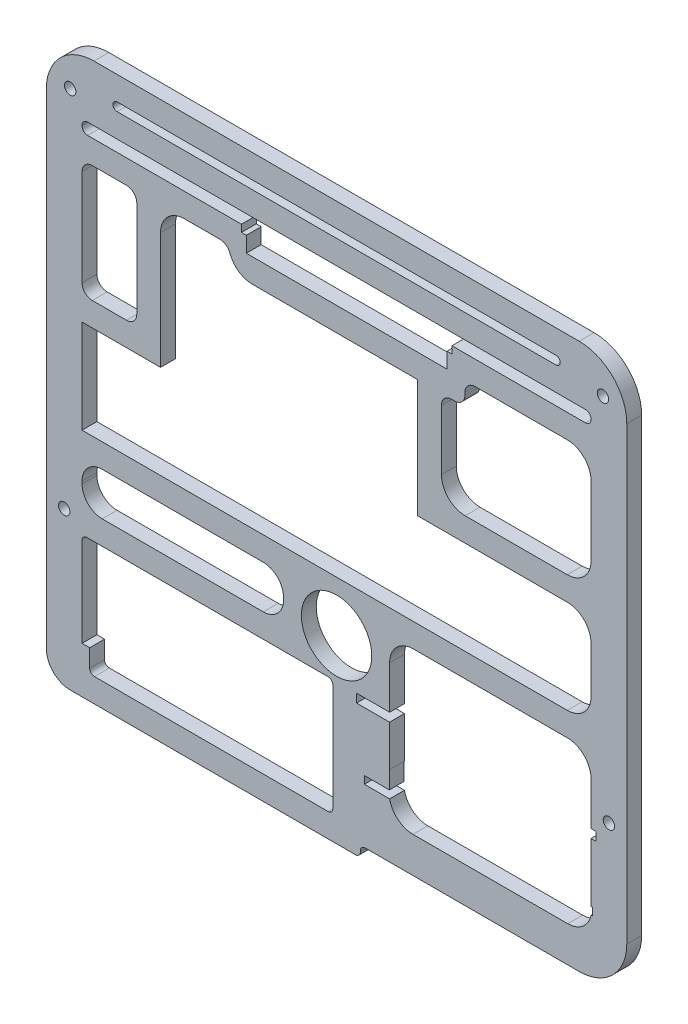
SolidWorks part; units mm, degrees
ref_plane "Front Plane" through (0, 0, 0) normal (0, 0, 1) x (1, 0, 0)
ref_plane "Top Plane" through (0, 0, 0) normal (0, 1, 0) x (1, 0, 0)
ref_plane "Right Plane" through (0, 0, 0) normal (1, 0, 0) x (0, 0, -1)
sketch "Sketch1" plane through (0, 0, 0) normal (0, 0, 1) x (1, 0, 0)
  line L0 (63.9883, 61.406) -> (63.9883, 57.596) construction
  line L1 (11.1776, 3.1158) -> (73.1542, 3.1158)
  line L2 (11.1776, 3.1158) -> (11.1776, 61.406)
  line L3 (11.1776, 61.406) -> (73.1542, 61.406)
  line L4 (73.1542, 3.1158) -> (73.1542, 61.406)
  line L5 (69.3442, 57.596) -> (14.9876, 57.596)
  line L6 (69.3442, 57.596) -> (69.3442, 6.9258)
  line L7 (69.3442, 6.9258) -> (14.9876, 6.9258)
  line L8 (14.9876, 57.596) -> (14.9876, 6.9258)
  line L9 (63.9883, 59.501) -> (18.0707, 59.501) construction
  line L10 (14.9876, 39.3805) -> (11.1776, 39.3805) construction
  line L11 (13.0826, 39.3805) -> (13.0826, 23.9527) construction
  line L12 (13.5248, 6.9258) -> (13.5248, 3.1158) construction
  line L13 (13.5248, 5.0208) -> (21.1598, 5.0208) construction
  line L14 (73.1542, 38.1916) -> (69.3442, 38.1916) construction
  line L15 (71.2492, 38.1916) -> (71.2492, 22.3321) construction
  line L16 (55.7422, 59.501) -> (30.5962, 59.501) construction
  line L19 (42.3087, 5.0208) -> (41.7626, 5.0208) construction
  line L21 (69.3442, 16.9588) -> (69.3442, 52.516) construction
  line L22 (14.9876, 47.563) -> (14.9876, 12.0058) construction
  dimension "D1" = 3.81
  dimension "D2" = 3.81
extrude "Boss-Extrude1" add sketch "Sketch1" along normal blind 1.5875
sketch "Sketch2" plane through (0, 0, 0) normal (0, 0, -1) x (-1, 0, 0)
  line L0 (-69.3442, 6.9258) -> (-69.3442, 57.596) construction
  line L1 (-69.3442, 26.6348) -> (-14.9876, 26.6348)
  line L2 (-69.3442, 26.6348) -> (-69.3442, 24.0948)
  line L3 (-69.3442, 24.0948) -> (-14.9876, 24.0948)
  line L4 (-14.9876, 26.6348) -> (-14.9876, 24.0948)
  line L5 (-14.9876, 57.596) -> (-14.9876, 6.9258) construction
  line L6 (-20.1206, 26.6348) -> (-57.8206, 26.6348) construction
  line L7 (-53.9642, 53.4304) -> (-53.9642, 51.7667)
  line L8 (-32.5266, 53.4304) -> (-32.0059, 53.4304)
  line L9 (-32.5266, 51.7667) -> (-53.9642, 51.7667) construction
  line L10 (-32.5266, 51.7667) -> (-32.5266, 53.4304) construction
  line L11 (-69.3442, 54.1924) -> (-54.4849, 54.1924)
  line L12 (-69.3442, 54.1924) -> (-69.3442, 51.6524)
  line L13 (-69.3442, 51.6524) -> (-55.8692, 51.6524)
  line L14 (-14.9876, 54.1924) -> (-14.9876, 51.6524)
  line L15 (-69.3442, 57.596) -> (-14.9876, 57.596)
  line L16 (-69.3442, 57.596) -> (-69.3442, 55.4243)
  line L17 (-69.3442, 55.4243) -> (-14.9876, 55.4243)
  line L18 (-14.9876, 57.596) -> (-14.9876, 55.4243)
  line L19 (-69.3442, 57.596) -> (-14.9876, 57.596) construction
  line L20 (-54.4849, 54.1924) -> (-54.4849, 53.4304)
  line L21 (-62.3462, 55.4243) -> (-23.9922, 55.4243) construction
  line L22 (-54.4849, 53.4304) -> (-53.9642, 53.4304)
  line L23 (-32.5266, 51.7667) -> (-53.9642, 51.7667)
  line L24 (-32.5266, 51.7667) -> (-32.5266, 53.4304)
  line L25 (-55.8692, 51.6524) -> (-55.8692, 49.2267)
  line L26 (-55.8692, 49.2267) -> (-30.6216, 49.2267)
  line L27 (-30.6216, 49.2267) -> (-30.6216, 51.6524)
  line L28 (-30.6216, 51.6524) -> (-14.9876, 51.6524)
  line L29 (-32.0059, 53.4304) -> (-32.0059, 54.1924)
  line L30 (-62.3462, 54.1924) -> (-23.9922, 54.1924) construction
  line L32 (-54.4849, 53.4304) -> (-54.4849, 54.1924) construction
  line L33 (-32.0059, 53.4304) -> (-54.4849, 53.4304) construction
  line L34 (-32.0059, 54.1924) -> (-14.9876, 54.1924)
  line L36 (-32.0059, 53.4304) -> (-32.0059, 54.1924) construction
  line L37 (-32.5266, 51.7667) -> (-32.5266, 53.4304) construction
  dimension "D1" = 2.54
  dimension "D2" = 1.905
  dimension "D3" = 2.54
  dimension "D4" = 1.905
  dimension "D5" = 2.54
extrude "Boss-Extrude2" add sketch "Sketch2" against normal up to surface (1.5875 mm away) up to face at (42.1659, 32.2609, 1.5875)
sketch "Sketch3" plane through (0, 0, 0) normal (0, 0, -1) x (-1, 0, 0)
  line L0 (-57.8206, 36.6348) -> (-50.8206, 36.6348) construction
  line L1 (-57.8206, 36.6348) -> (-50.8206, 36.6348)
  line L2 (-57.8206, 36.6348) -> (-69.3442, 36.6348)
  line L3 (-69.3442, 26.6348) -> (-69.3442, 51.6524) construction
  line L4 (-69.3442, 36.6348) -> (-69.3442, 39.1748)
  line L5 (-69.3442, 39.1748) -> (-53.3606, 39.1748)
  line L6 (-50.8206, 28.408) -> (-50.8206, 36.6348)
  line L7 (-50.8206, 28.408) -> (-50.8206, 49.2267)
  line L8 (-55.8692, 49.2267) -> (-30.6216, 49.2267) construction
  line L9 (-50.8206, 49.2267) -> (-53.3606, 49.2267)
  line L10 (-53.3606, 49.2267) -> (-53.3606, 39.1748)
  line L11 (-23.3706, 36.6348) -> (-20.1206, 36.6348) construction
  line L12 (-23.3706, 36.6348) -> (-20.1206, 36.6348)
  line L13 (-20.1206, 36.6348) -> (-14.9876, 36.6348)
  line L14 (-14.9876, 51.6524) -> (-14.9876, 26.6348) construction
  line L15 (-14.9876, 36.6348) -> (-14.9876, 39.1748)
  line L16 (-14.9876, 39.1748) -> (-20.8306, 39.1748)
  line L17 (-20.8306, 39.1748) -> (-20.8306, 51.6524)
  line L18 (-30.6216, 51.6524) -> (-14.9876, 51.6524) construction
  line L19 (-20.8306, 51.6524) -> (-23.3706, 51.6524)
  line L20 (-23.3706, 51.6524) -> (-23.3706, 36.6348)
  line L21 (-23.3706, 36.6348) -> (-16.2412, 25.8471)
  line M22 (-69.3442, 26.6348) -> (-69.3442, 51.6524)
  line M25 (-55.8692, 49.2267) -> (-30.6216, 49.2267)
  line M27 (-30.6216, 51.6524) -> (-14.9876, 51.6524)
  line M28 (-14.9876, 51.6524) -> (-14.9876, 26.6348)
  dimension "D1" = 2.54
  dimension "D2" = 2.54
  dimension "D3" = 2.54
  dimension "D4" = 2.54
extrude "Boss-Extrude3" add sketch "Sketch3" against normal up to surface (1.5875 mm away) contours L10 L5 L2 L1 L6 L7 M25 M22 | L20 L12 L13 L16 L17 M27 M28 region at (63.5824, 36.8588, 0) region at (20.9265, 42.3962, 0) up to face at (42.8855, 53.7395, 1.5875)
sketch "Sketch4" plane through (0, 0, 0) normal (0, 0, -1) x (-1, 0, 0)
  line L0 (-69.3442, 24.0948) -> (-14.9876, 24.0948) construction
  line L1 (-47.8301, 24.0948) -> (-36.5017, 24.0948)
  line L2 (-47.8301, 24.0948) -> (-47.8301, 6.9258)
  line L3 (-47.8301, 6.9258) -> (-36.5017, 6.9258)
  line L4 (-36.5017, 24.0948) -> (-36.5017, 6.9258)
  line L5 (-14.9876, 6.9258) -> (-69.3442, 6.9258) construction
  line L6 (-45.9251, 21.2246) -> (-47.8301, 21.2246) construction
  line L7 (-38.4067, 21.2246) -> (-36.5017, 21.2246) construction
  circle A0 centre (-42.1659, 21.2246) radius 3.7592 construction
  dimension "D1" = 1.905
extrude "Boss-Extrude4" add sketch "Sketch4" against normal up to surface (1.5875 mm away) up to face at (17.9091, 45.4136, 1.5875)
sketch "Sketch5" plane through (0, 0, 0) normal (0, 0, -1) x (-1, 0, 0)
  line L0 (-15.8038, 16.9715) -> (-41.7626, 16.9715) construction
  line L3 (-41.7626, 4.5128) -> (-41.7626, 16.9715) construction
  line L4 (-15.8038, 4.5128) -> (-41.7626, 4.5128) construction
  line L5 (-15.8038, 4.5128) -> (-15.8038, 16.9715) construction
  line L6 (-15.8038, 16.9715) -> (-41.7626, 16.9715)
  line L7 (-41.7626, 4.5128) -> (-41.7626, 16.9715)
  line L8 (-15.8038, 4.5128) -> (-41.7626, 4.5128)
  line L9 (-15.8038, 4.5128) -> (-15.8038, 16.9715)
  circle A0 centre (-42.1659, 21.2246) radius 3.7592 construction
  circle A1 centre (-42.1659, 21.2246) radius 3.7592
extrude "Cut-Extrude1" cut sketch "Sketch5" against normal up to surface (1.5875 mm away) up to face at (58.5871, 15.5103, 1.5875)
sketch "Sketch8" plane through (0, 0, 0) normal (0, 0, -1) x (-1, 0, 0)
  line L1 (-36.5017, 16.9715) -> (-14.9876, 16.9715)
  line L2 (-36.5017, 16.9715) -> (-36.5017, 19.5115)
  line L3 (-36.5017, 19.5115) -> (-14.9876, 19.5115)
  line L4 (-14.9876, 16.9715) -> (-14.9876, 19.5115)
  line L5 (-14.9876, 24.0948) -> (-14.9876, 6.9258) construction
  dimension "D1" = 2.54
extrude "Boss-Extrude5" add sketch "Sketch8" against normal up to surface (1.5875 mm away) up to face at (38.4067, 21.2246, 1.5875)
fillet "Fillet1" radius 5.08 3 edges at (73.1542, 3.1158, 0.7937) (11.1776, 61.406, 0.7937) (73.1542, 61.406, 0.7937)
fillet "Fillet2" radius 2.54 7 edges at (23.3706, 51.6524, 0.7937) (30.6216, 49.2267, 0.7937) (69.3442, 51.6524, 0.7937) (53.3606, 39.1748, 0.7937) (69.3442, 26.6348, 0.7937) (69.3442, 39.1748, 0.7937) (69.3442, 36.6348, 0.7937)
fillet "Fillet3" radius 1.0922 8 edges at (53.3606, 49.2267, 0.7937) (55.8692, 49.2267, 0.7937) (55.8692, 51.6524, 0.7937) (14.9876, 39.1748, 0.7937) (20.8306, 39.1748, 0.7937) (14.9876, 51.6524, 0.7937) (20.8306, 51.6524, 0.7937) (30.6216, 51.6524, 0.7937)
fillet "Fillet4" radius 0.5842 4 edges at (14.9876, 55.4243, 0.7937) (69.3442, 55.4243, 0.7937) (69.3442, 54.1924, 0.7937) (14.9876, 54.1924, 0.7937)
fillet "Fillet8" radius 2.159 4 edges at (36.5017, 19.5115, 0.7937) (36.5017, 24.0948, 0.7937) (14.9876, 24.0948, 0.7938) (14.9876, 19.5115, 0.7937)
sketch "Sketch6" plane through (0, 0, 0) normal (0, 0, -1) x (-1, 0, 0)
  line L0 (-16.6206, 28.1348) -> (-18.1206, 26.6348) construction
  line L1 (-18.1206, 36.6348) -> (-16.6206, 35.1348) construction
  line L2 (-16.6206, 35.1348) -> (-16.6206, 28.1348) construction
  line L3 (-16.6206, 28.1348) -> (-18.1206, 26.6348)
  line L4 (-18.1206, 36.6348) -> (-16.6206, 35.1348)
  line L5 (-16.6206, 35.1348) -> (-16.6206, 28.1348)
  line L6 (-18.1206, 36.6348) -> (-18.1206, 26.6348)
  circle A0 centre (-71.2492, 18.4306) radius 0.6096 construction
  circle A1 centre (-71.2492, 18.4306) radius 0.6096
  circle A4 centre (-70.6142, 57.596) radius 0.6096 construction
  circle A5 centre (-70.6142, 57.596) radius 0.6096
  circle A6 centre (-13.0826, 18.4306) radius 0.6096 construction
  circle A7 centre (-13.0826, 18.4306) radius 0.6096
  circle A10 centre (-13.7176, 57.596) radius 0.6096 construction
  circle A11 centre (-13.7176, 57.596) radius 0.6096
extrude "Cut-Extrude2" cut sketch "Sketch6" against normal up to surface (1.5875 mm away) up to face at (24.1846, 9.4701, 1.5875)
sketch "Sketch7" plane through (0, 0, 0) normal (0, 0, -1) x (-1, 0, 0)
  line L0 (-44.3026, 16.9715) -> (-69.8804, 16.9715) construction
  line L1 (-69.8804, 16.9715) -> (-69.8804, 16.0571) construction
  line L2 (-69.8804, 16.0571) -> (-44.3026, 16.0571) construction
  line L3 (-44.3026, 16.0571) -> (-44.3026, 16.9715) construction
  line L4 (-45.1366, 9.7751) -> (-69.5206, 9.7751) construction
  line L5 (-69.5206, 9.7751) -> (-69.5206, 8.9623) construction
  line L6 (-69.5206, 8.9623) -> (-45.1366, 8.9623) construction
  line L7 (-45.1366, 8.9623) -> (-45.1366, 9.7751) construction
  line L8 (-44.3026, 16.9715) -> (-69.8804, 16.9715)
  line L9 (-69.8804, 16.9715) -> (-69.8804, 16.0571)
  line L10 (-69.8804, 16.0571) -> (-44.3026, 16.0571)
  line L11 (-44.3026, 16.0571) -> (-44.3026, 16.9715)
  line L12 (-45.1366, 9.7751) -> (-69.5206, 9.7751)
  line L13 (-69.5206, 9.7751) -> (-69.5206, 8.9623)
  line L14 (-69.5206, 8.9623) -> (-45.1366, 8.9623)
  line L15 (-45.1366, 8.9623) -> (-45.1366, 9.7751)
  line L20 (-66.8536, 9.7751) -> (-47.8036, 9.7751)
  line L21 (-47.8036, 9.7751) -> (-47.8036, 11.6547)
  line L22 (-47.8036, 11.6547) -> (-66.8536, 11.6547)
  line L23 (-66.8536, 11.6547) -> (-66.8536, 9.7751)
  line L24 (-66.8536, 9.7751) -> (-47.8036, 9.7751)
  line L25 (-47.8036, 9.7751) -> (-47.8036, 11.6547)
  line L26 (-47.8036, 11.6547) -> (-66.8536, 11.6547)
  line L27 (-66.8536, 11.6547) -> (-66.8536, 9.7751)
  dimension "D1" = 0
extrude "Cut-Extrude3" cut sketch "Sketch7" against normal up to surface (1.5875 mm away) contours L14 L15 L12 L13 | L26 L27 L12 L25 | L10 L11 L8 L9 region at (57.0915, 16.5143, 0) region at (57.3286, 9.3687, 0) region at (57.3286, 10.7149, 0) up to face at (13.108, 57.596, 1.5875)
fillet "Fillet6" radius 0.508 4 edges at (41.7626, 16.9715, 0.7937) (41.7626, 4.5128, 0.7937) (15.8038, 4.5128, 0.7937) (14.9876, 16.9715, 0.7937)
sketch "Sketch9" plane through (0, 0, 1.5875) normal (0, 0, 1) x (1, 0, 0)
  line L0 (68.0742, 61.406) -> (16.2576, 61.406) construction
  line L1 (18.2896, 58.866) -> (66.0422, 58.866)
  line L2 (18.2896, 58.866) -> (18.2896, 57.9643)
  line L3 (18.2896, 57.9643) -> (66.0422, 57.9643)
  line L8 (66.0422, 58.866) -> (66.0422, 57.9643)
  line L9 (15.5718, 55.4243) -> (68.76, 55.4243) construction
  line L10 (11.1776, 56.326) -> (11.1776, 59.3208) construction
  line L11 (18.2896, 58.866) -> (11.1776, 58.866) construction
  line L13 (66.0422, 58.866) -> (73.1542, 58.866) construction
  line L14 (73.1542, 56.326) -> (73.1542, 56.8419) construction
  dimension "D1" = 2.54
  dimension "D2" = 2.54
  dimension "D3" = 7.112
extrude "Cut-Extrude4" cut sketch "Sketch9" against normal up to surface (1.5875 mm away) up to face at (57.106, 13.2916, 0)
fillet "Fillet7" radius 0.4318 4 edges at (18.2896, 57.9643, 0.7937) (18.2896, 58.866, 0.7937) (66.0422, 57.9643, 0.7937) (66.0422, 58.866, 0.7937)
fillet "Fillet9" radius 2.54 4 edges at (69.3442, 6.9258, 0.7937) (47.8301, 6.9258, 0.7937) (69.3442, 24.0948, 0.7937) (47.8301, 24.0948, 0.7937)
sketch "Sketch10" plane through (0, 0, 1.5875) normal (0, 0, 1) x (1, 0, 0)
  line L0 (42.1659, 24.9838) -> (42.1659, -13.4858) construction
  line L1 (11.1776, 3.1158) -> (44.7059, 3.1158)
  line L2 (11.1776, 3.1158) -> (11.1776, 1.9728)
  line L3 (11.1776, 1.9728) -> (44.7059, 1.9728)
  line L4 (44.7059, 3.1158) -> (44.7059, 1.9728)
  line L5 (16.3118, 4.5128) -> (41.2546, 4.5128) construction
  circle A0 centre (42.1659, 21.2246) radius 3.7592 construction
  dimension "D1" = 2.54
  dimension "D2" = 2.54
extrude "Boss-Extrude6" add sketch "Sketch10" against normal up to surface (1.5875 mm away) up to face at (42.1659, 58.4152, 0)
fillet "Fillet10" radius 2.54 1 edges at (11.1776, 1.9728, 0.7937)
fillet "Fillet11" radius 0.508 2 edges at (44.7059, 3.1158, 0.7937) (44.7059, 1.9728, 0.7937)
